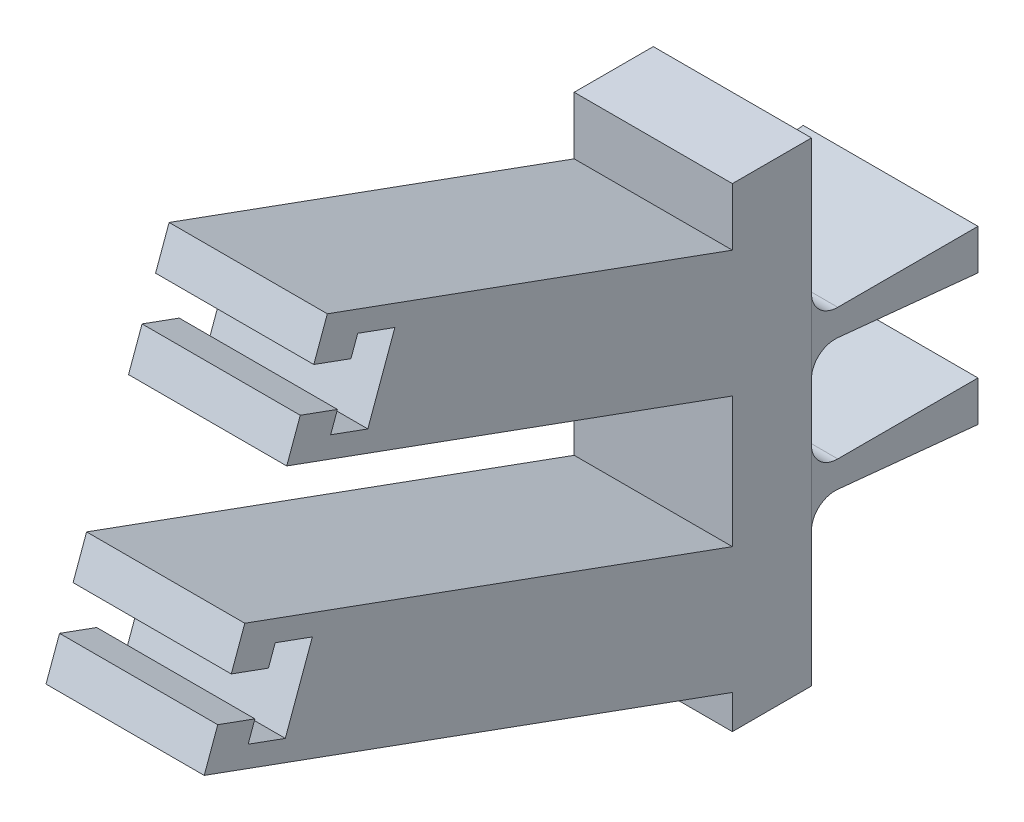
SolidWorks part; units mm, degrees
ref_plane "Front Plane" through (0, 0, 0) normal (0, 0, 1) x (1, 0, 0)
ref_plane "Top Plane" through (0, 0, 0) normal (0, 1, 0) x (1, 0, 0)
ref_plane "Right Plane" through (0, 0, 0) normal (1, 0, 0) x (0, 0, -1)
sketch "Sketch1" plane through (0, 0, 0) normal (0, 0, 1) x (1, 0, 0)
  line L1 (0, 0) -> (20, 0)
  line L2 (0, 0) -> (0, 60)
  line L3 (0, 60) -> (20, 60)
  line L4 (20, 0) -> (20, 60)
  dimension "D1" = 20
  dimension "D2" = 60
extrude "Boss-Extrude1" add sketch "Sketch1" along normal blind 10
sketch "Sketch3" plane through (0, 0, 0) normal (0, 0, -1) x (-1, 0, 0)
  line L0 (-20, 30) -> (0, 30) construction
  line L1 (-20, 0) -> (-20, 60) construction
  line L2 (0, 0) -> (0, 60) construction
  line L3 (-10, 60) -> (-10, 0) construction
  line L4 (0, 60) -> (-20, 60) construction
  line L5 (0, 0) -> (-20, 0) construction
  line L7 (-20, 20.2) -> (0, 20.2)
  line L8 (-20, 20.2) -> (-20, 39.8)
  line L9 (-20, 39.8) -> (0, 39.8)
  line L10 (0, 20.2) -> (0, 39.8)
  line L11 (-20, 23.2) -> (0, 23.2)
  line L12 (-20, 23.2) -> (-20, 36.8)
  line L13 (-20, 36.8) -> (0, 36.8)
  line L14 (0, 23.2) -> (0, 36.8)
  line M1 (0, 0) -> (0, 60)
  line M3 (-20, 60) -> (-20, 0)
  dimension "D1" = 13.6
  dimension "D2" = 3
extrude "Boss-Extrude2" add sketch "Sketch3" along normal blind 20 draft 3 contours L13 L9 M3 M1 | L11 L8 L7 M1 region at (10, 21.7, 0) region at (10, 38.3, 0) draft outward yes
fillet "Fillet1" radius 3 4 edges at (10, 23.2, 0) (10, 36.8, 0) (10, 20.2, 0) (10, 39.8, 0)
sketch "Sketch5" plane through (0, 0, 10) normal (0, 0, 1) x (1, 0, 0)
  line L0 (0, 60) -> (0, 0) construction
  line L2 (0, 7.795) -> (0, 11.0287)
  line L4 (20, 7.795) -> (20, 11.0287)
  line L5 (10, 60) -> (10, 0) construction
  line L6 (20, 60) -> (0, 60) construction
  line L7 (0, 0) -> (20, 0) construction
  line L8 (0, 30) -> (20, 30) construction
  line L9 (20, 0) -> (20, 60) construction
  line L12 (0, 18.6043) -> (0, 15.3412)
  line L14 (20, 18.6043) -> (20, 15.3412)
ref_plane "Plane1" through (0, 10.2326, 28.1139) normal (0, 0.342, 0.9397) x (-1, 0, 0)
sketch "Sketch7" plane through (0, 10.2326, 28.1139) normal (0, 0.342, 0.9397) x (-1, 0, 0)
  line L1 (0, -0.6133) -> (-20, -0.6133)
  line L2 (0, -0.6133) -> (0, -15.6133)
  line L3 (0, -15.6133) -> (-20, -15.6133)
  line L4 (-20, -0.6133) -> (-20, -15.6133)
  line L9 (-20, 3.4202) -> (-20, -52.9614) construction
  line L10 (0, -52.9614) -> (0, 3.4202) construction
  line L11 (-10, -15.6133) -> (-10, 3.2811) construction
  line L12 (-20, 0) -> (-20, -56.3816) construction
  dimension "D1" = 15
extrude "Boss-Extrude3" add sketch "Sketch7" along normal blind 52 and the other way up to surface contours L1 L4 L3 L2 region at (10, 17.8566, 25.3389) other way up to face at (10, 30, 10)
ref_plane "Plane2" through (0, 28.0177, 76.9779) normal (0, 0.342, 0.9397) x (1, 0, 0)
sketch "Sketch11" plane through (0, 10.2326, 28.1139) normal (0, 0.342, 0.9397) x (-1, 0, 0)
  line L0 (0, -52.9614) -> (0, -15.6133) construction
  line L1 (0, -31.1133) -> (-20, -31.1133)
  line L2 (0, -31.1133) -> (0, -46.1133)
  line L3 (0, -46.1133) -> (-20, -46.1133)
  line L4 (-20, -31.1133) -> (-20, -46.1133)
  line L5 (-20, -15.6133) -> (-20, -52.9614) construction
  line L6 (0, -15.6133) -> (-20, -15.6133) construction
  dimension "D1" = 15
  dimension "D2" = 15.5
extrude "Boss-Extrude4" add sketch "Sketch11" against normal up to surface and the other way up to surface (52 mm away) up to face at (10, 40.1275, 10) other way up to plane "Plane2"
sketch "Sketch9" plane through (0, 0, 0) normal (-1, 0, 0) x (0, 0, 1)
  line L0 (68.6494, 36.2808) -> (67.7944, 38.6301)
  line L1 (63.0959, 36.92) -> (67.7944, 38.6301)
  line L2 (63.0959, 36.92) -> (66.5161, 27.523)
  line L3 (66.5161, 27.523) -> (71.2146, 29.2331)
  line L4 (71.2146, 29.2331) -> (70.3595, 31.5824)
  line L5 (75.058, 33.2925) -> (70.3595, 31.5824)
  line L7 (68.6494, 36.2808) -> (73.3479, 37.9909)
  line L8 (74.2029, 35.6417) -> (16.049, 14.4754) construction
  line L9 (10, 20.2551) -> (71.6378, 42.6894) construction
  line L10 (10, 4.2924) -> (76.7681, 28.594) construction
  line L12 (10, 4.2924) -> (76.7681, 28.594) construction
  line L13 (76.7681, 28.594) -> (71.6378, 42.6894) construction
  line L14 (35.6031, 62.0313) -> (51.165, 19.2752) construction
  line L15 (10, 52.7125) -> (61.2062, 71.35) construction
  line L16 (68.9871, 49.972) -> (10, 28.5024) construction
  line L17 (61.2062, 71.35) -> (66.3365, 57.2546) construction
  line L19 (10, 36.7498) -> (10, 20.2551) construction
  point P17 (64.806, 32.2215)
  point P27 (22.0413, 47.9271)
  point P28 (43.384, 40.6532)
  dimension "D1" = 5
  dimension "D2" = 5
  dimension "D3" = 10
  dimension "D4" = 5
extrude "Cut-Extrude2" cut sketch "Sketch9" against normal blind 20 and the other way through all flip side to cut
ref_plane "Plane3" through (0, 21.9544, -7.9907) normal (0, -0.9397, 0.342) x (-1, 0, 0)
mirror "Mirror1" about plane through (0, 21.9544, -7.9907) normal (0, -0.9397, 0.342) of "Cut-Extrude2"
